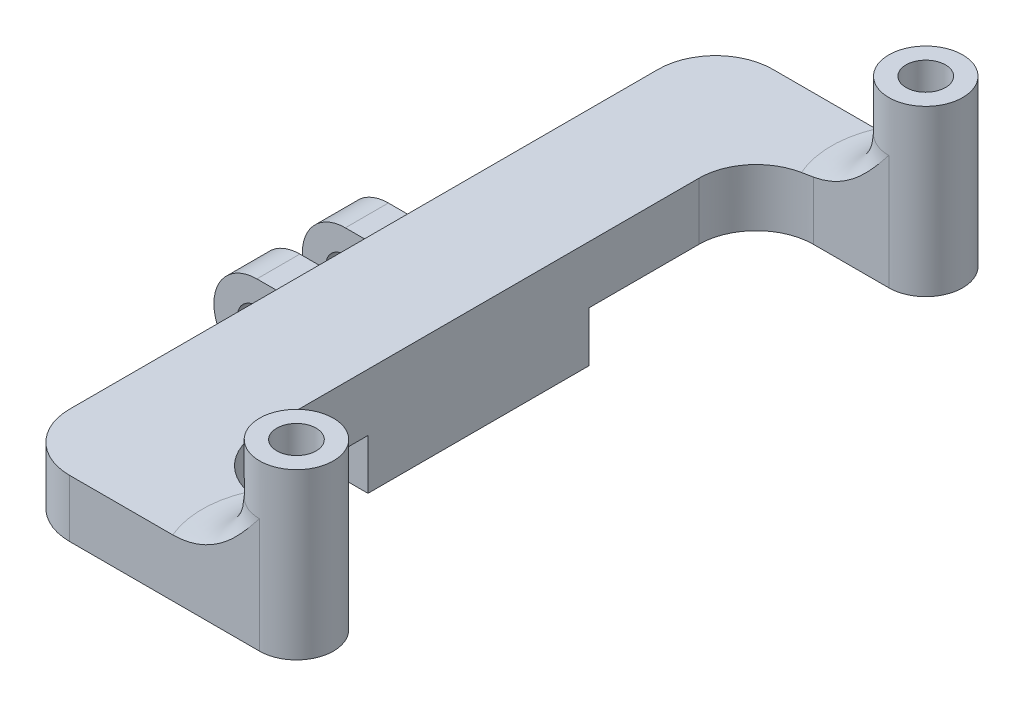
SolidWorks part; units mm, degrees
material "CARBON FIBER TEST"
ref_plane "Front Plane" through (0, 0, 0) normal (0, 0, 1) x (1, 0, 0)
ref_plane "Top Plane" through (0, 0, 0) normal (0, 1, 0) x (1, 0, 0)
ref_plane "Right Plane" through (0, 0, 0) normal (1, 0, 0) x (0, 0, -1)
sketch "Sketch2" plane through (0, 0, 0) normal (0, 0, 1) x (1, 0, 0)
  line L0 (0, 1.75) -> (8, 1.75)
  line L1 (8, 1.75) -> (8, -1.75)
  line L2 (8, -1.75) -> (0, -1.75)
  line L3 (0, -1.75) -> (0, 1.75)
  point P4 (0, 0)
  dimension "D2" = 3.5
  dimension "D3" = 8
extrude "Boss-Extrude1" add sketch "Sketch2" along normal mid plane 15.43
sketch "Sketch4" plane through (0, 0, 7.715) normal (0, 0, 1) x (1, 0, 0)
  line L0 (0, 4.25) -> (-2.8368, 4.25)
  line L1 (0, -1.75) -> (-2.8368, -1.75)
  line L2 (0, 4.25) -> (0, -1.75)
  arc A0 (-2.8368, 4.25) -> (-2.8368, -1.75) centre (-2.8368, 1.25) ccw
  circle A1 centre (-2.8368, 1.25) radius 1.375
  dimension "D1" = 6
  dimension "D3" = 2.75
  dimension "D2" = 3.1
extrude "Boss-Extrude2" add sketch "Sketch4" against normal blind 3 from offset 3.086 offset against normal yes
pattern_linear "LPattern1" count 2 spacing 6.172 along (0, 0, -1) of "Boss-Extrude2"
sketch "Sketch6" plane through (0, 1.75, 0) normal (0, 1, 0) x (1, 0, 0)
  line L3 (0, 24.535) -> (0, -24.535)
  line L4 (0, -24.535) -> (17.25, -24.535)
  line L6 (17.25, -19.375) -> (8, -19.375)
  line L7 (8, -19.375) -> (8, 19.375)
  line L8 (8, 19.375) -> (17.25, 19.375)
  line L10 (17.25, 24.535) -> (0, 24.535)
  arc A0 (17.25, 19.375) -> (17.25, 24.535) centre (17.25, 21.955) ccw
  arc A1 (17.25, -24.535) -> (17.25, -19.375) centre (17.25, -21.955) ccw
  dimension "D5" = 2.58
  dimension "D1" = 8
  dimension "D2" = 9.25
  dimension "D3" = 43.91
extrude "Boss-Extrude3" add sketch "Sketch6" along normal blind 4
sketch "Sketch7" plane through (0, 5.75, 0) normal (0, 1, 0) x (1, 0, 0)
  circle A0 centre (17.25, 21.955) radius 2.58
  circle A1 centre (17.25, -21.955) radius 2.58
  arc A6 (17.25, 19.375) -> (17.25, 24.535) centre (17.25, 21.955) ccw construction
  arc A7 (17.25, -24.535) -> (17.25, -19.375) centre (17.25, -21.955) ccw construction
  dimension "D1" = 2.58
extrude "Boss-Extrude4" add sketch "Sketch7" along normal offset from surface (7.5 mm away) 15 up to face at (0.3877, -1.75, 0.0287)
sketch "Sketch8" plane through (0, 13.25, 0) normal (0, 1, 0) x (1, 0, 0)
  circle A0 centre (17.25, 21.955) radius 1.375
  circle A1 centre (17.25, -21.955) radius 1.375
  circle A2 centre (17.25, -21.955) radius 2.58 construction
  circle A4 centre (17.25, 21.955) radius 2.58 construction
  dimension "D1" = 2.75
extrude "Cut-Extrude1" cut sketch "Sketch8" against normal through all
fillet "Fillet1" radius 4 4 edges at (14.67, 5.75, 21.955) (14.67, 5.75, -21.955) (0, 3.75, -24.535) (0, 3.75, 24.535)
fillet "Fillet2" radius 4 2 edges at (8, 3.75, -19.375) (8, 3.75, 19.375)
equation "\"D19@Boss-Extrude2\"=(15.43mm/5)"
equation "\"D3@LPattern1\"=(15.43/5*2)"
